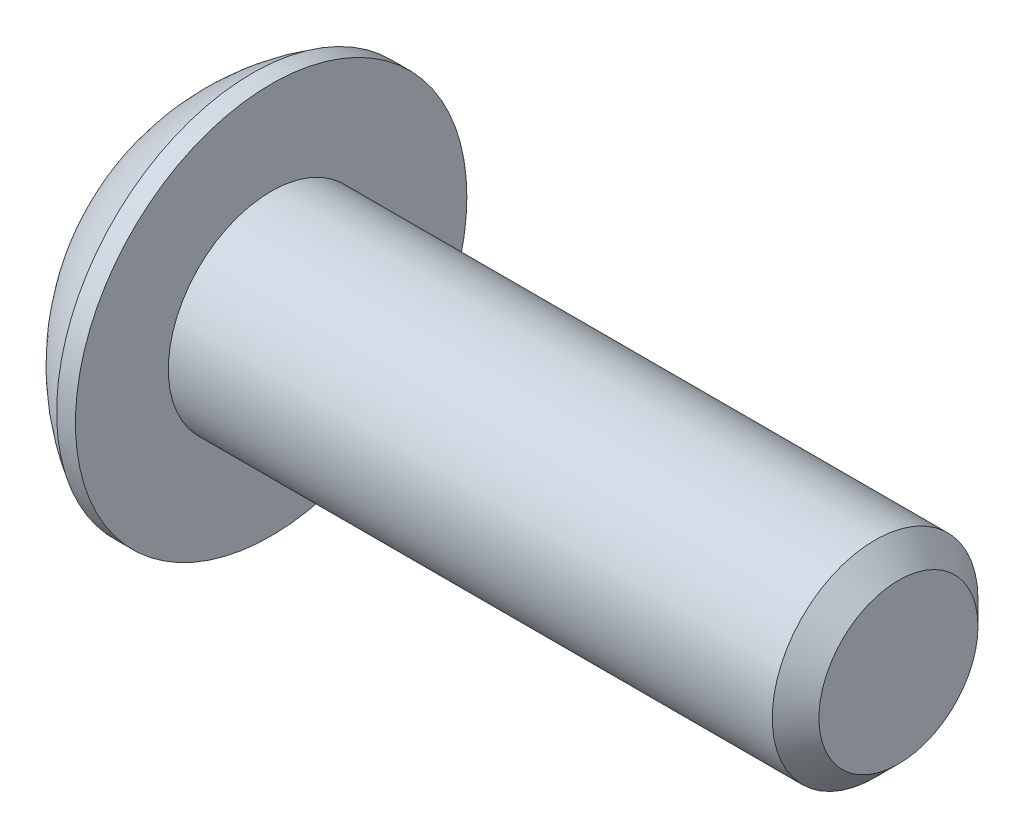
SolidWorks part; units mm, degrees
material "Cast Carbon Steel"
ref_plane "Front Plane" through (0, 0, 0) normal (0, 0, 1) x (1, 0, 0)
ref_plane "Top Plane" through (0, 0, 0) normal (0, 1, 0) x (1, 0, 0)
ref_plane "Right Plane" through (0, 0, 0) normal (1, 0, 0) x (0, 0, -1)
sketch "Sketch1" plane through (0, 0, 0) normal (0, 0, 1) x (1, 0, 0)
  line L0 (7.4549, 0) -> (-7.4549, 0) construction
  line L1 (7.4549, 0) -> (-7.4549, 0)
  line L14 (7.4549, 0) -> (7.4549, 2.0828)
  line L16 (7.4549, 2.0828) -> (-5.2451, 2.0828)
  line L17 (-5.2451, 2.0828) -> (-5.2451, 3.9624)
  line L18 (-5.2451, 3.9624) -> (-5.6261, 3.9624)
  line L19 (-7.4549, 1.9812) -> (-7.4549, 0)
  arc A1 (-5.6261, 3.9624) -> (-7.4549, 1.9812) centre (-3.321, 0) ccw
  dimension "D1" = 4.5841
  dimension "D2" = 7.9248
  dimension "D3" = 4.1656
  dimension "D4" = 2.2098
  dimension "D5" = 12.7
  dimension "D6" = 0.381
  dimension "D7" = 1.9812
revolve "Revolve2" add sketch "Sketch1" angle 360 about L0
cosmetic thread "Cosmetic Thread1" parameters "D1"=11, "D2"=3
sketch "Sketch4" plane through (-7.4549, 0, 0) normal (-1, 0, 0) x (0, 0, 1)
  point P0 (0, 0)
sketch "Sketch9" plane through (-7.4549, 0, 0) normal (-1, 0, 0) x (0, 0, 1)
  line L0 (0, 1.3785) -> (1.1938, 0.6892)
  line L1 (1.1938, -0.6892) -> (0, -1.3785)
  line L2 (0, -1.3785) -> (-1.1938, -0.6892)
  line L3 (-1.1938, -0.6892) -> (-1.1938, 0.6892)
  line L4 (-1.1938, 0.6892) -> (0, 1.3785)
  line L5 (1.1938, 0.6892) -> (-1.1938, -0.6892) construction
  line L6 (1.1938, 0.6892) -> (1.1938, -0.6892)
  line L7 (-1.1938, 0.6892) -> (1.1938, -0.6892) construction
  line L8 (0, 1.3785) -> (0, -1.3785) construction
  point P7 (0, 0)
  dimension "D1" = 2.3876
extrude "Cut-Extrude1" cut sketch "Sketch9" against normal blind 1.3208
hole_wizard "Tapped Hole1" positions "3DSketch3" profile "Sketch5" tap size "M2.5x0.45" standard "JIS"
sketch3d "3DSketch3"
  point P0 (-7.4549, 0, 0)
sketch "Sketch5" plane through (-7.4549, 0, 0) normal (0, 1, 0) x (0, 0, 1)
  line L0 (0, 0) -> (0, 2.0094)
  line L1 (0, 2.0094) -> (1.194, 1.32)
  line L2 (1.194, 1.32) -> (1.194, 0)
  line L5 (1.194, 0) -> (0, 0)
  line L10 (0, 2.0094) -> (-1.194, 1.32) construction
  line L11 (0, -6.35) -> (0, 107.95) construction
  dimension "Tap Drill Dia." = 2.388
  dimension "Tap Drill Depth" = 1.32
  dimension "Drill Angle" = 120
chamfer "Chamfer1" distance 0.4724 angle 45 1 edges at (7.4549, 0, -2.0828)
ref_axis "Axis1" through (-8.9418, 0, 0) along (1, 0, 0)
ref_plane "Plane1" through (-0.0751, 0, 0) normal (1, 0, 0) x (0, 0, -1)
ref_plane "Plane2" through (-1.6451, 0, 0) normal (1, 0, 0) x (0, 0, -1)
